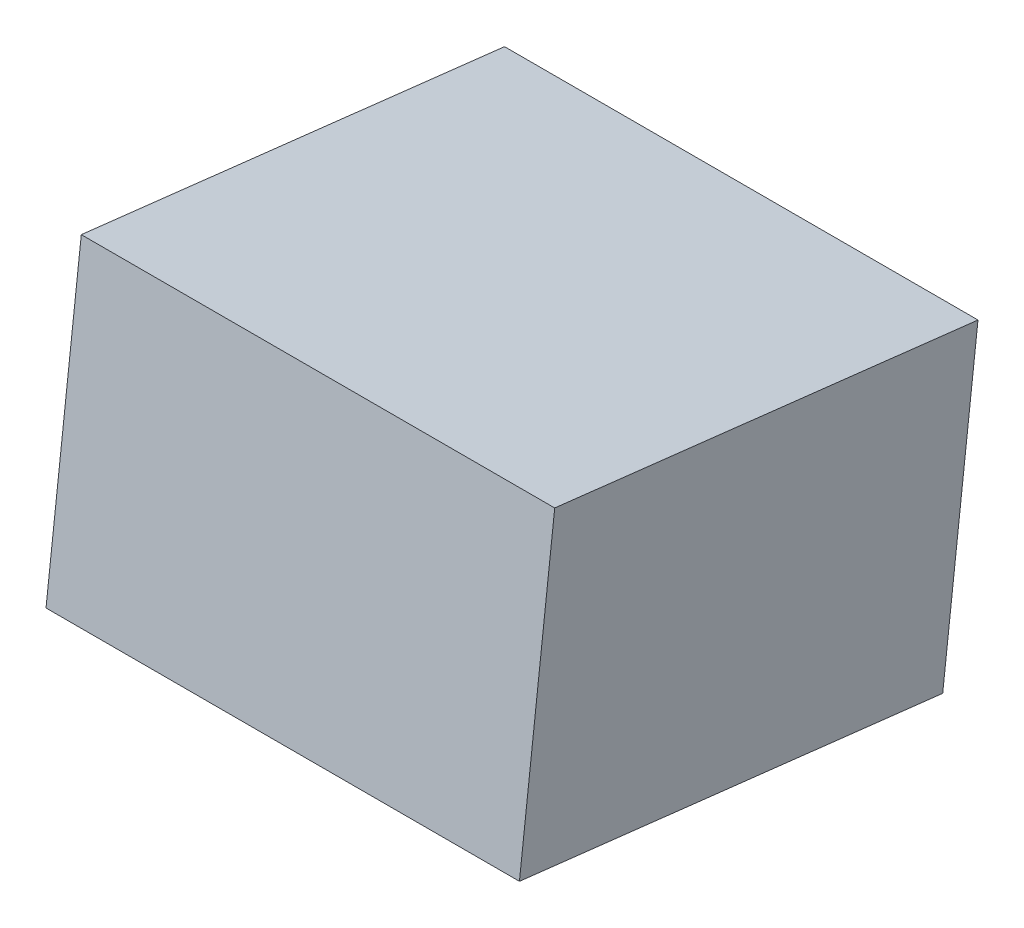
SolidWorks part; units mm, degrees
ref_plane "Front Plane" through (0, 0, 0) normal (0, 0, 1) x (1, 0, 0)
ref_plane "Top Plane" through (0, 0, 0) normal (0, 1, 0) x (1, 0, 0)
ref_plane "Right Plane" through (0, 0, 0) normal (1, 0, 0) x (0, 0, -1)
sketch "Sketch1" plane through (0, 343.9788, -39.7026) normal (0, 0.9934, -0.1147) x (1, 0, 0)
  line L1 (-235, 60.2443) -> (-35, 60.2443)
  line L2 (-235, 60.2443) -> (-235, 240.2443)
  line L3 (-235, 240.2443) -> (-35, 240.2443)
  line L4 (-35, 60.2443) -> (-35, 240.2443)
  line L5 (-235, 60.2443) -> (-35, 240.2443) construction
  line L6 (-235, 240.2443) -> (-35, 60.2443) construction
  point P0 (-135, 150.2443)
  dimension "D1" = 180
  dimension "D2" = 200
extrude "Boss-Extrude1" add sketch "Sketch1" along normal blind 130
